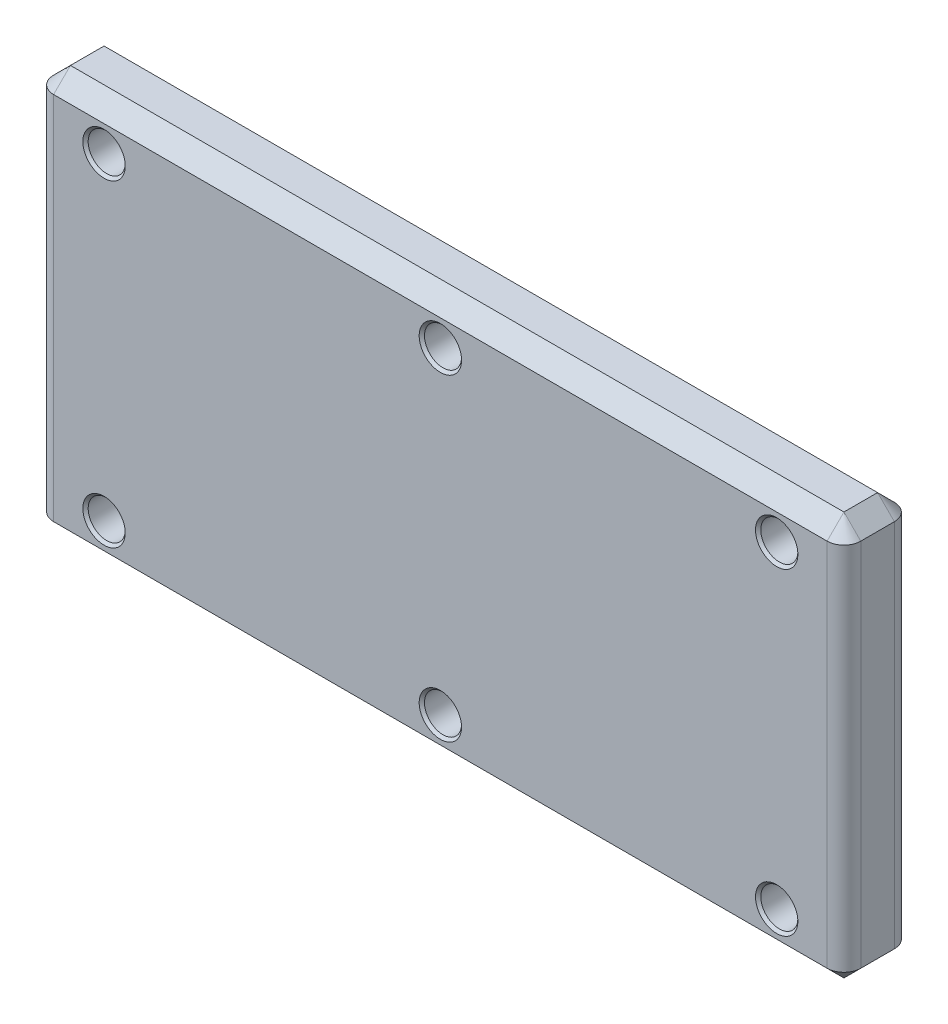
SolidWorks part; units mm, degrees
material "ABS"
ref_plane "Front Plane" through (0, 0, 0) normal (0, 0, 1) x (1, 0, 0)
ref_plane "Top Plane" through (0, 0, 0) normal (0, 1, 0) x (1, 0, 0)
ref_plane "Right Plane" through (0, 0, 0) normal (1, 0, 0) x (0, 0, -1)
ref_axis "X Axis" through (88.99, 0, 0) along (-1, 0, 0)
ref_axis "Y Axis" through (0, 55, 0) along (0, -1, 0)
ref_axis "Z Axis" through (0, 0, -88.99) along (0, 0, 1)
sketch "Sketch1" plane through (0, 0, 0) normal (0, 0, 1) x (1, 0, 0)
  line L1 (38.1, -19.05) -> (-38.1, -19.05)
  line L2 (38.1, -19.05) -> (38.1, 19.05)
  line L3 (38.1, 19.05) -> (-38.1, 19.05)
  line L4 (-38.1, -19.05) -> (-38.1, 19.05)
  line L5 (0, 19.05) -> (0, -19.05) construction
  line L6 (38.1, 0) -> (-38.1, 0) construction
  point P0 (0, 0)
  dimension "D1" = 76.2
  dimension "D2" = 38.1
extrude "Boss-Extrude1" add sketch "Sketch1" along normal mid plane 6.35
extrude "Boss-Extrude2" add sketch "Sketch1<2>" along normal mid plane 6.35
sketch "Sketch1<2>" plane through (0, 0, 0) normal (0, 0, 1) x (1, 0, 0) same geometry as "Sketch1"
sketch "Sketch8" plane through (0, 0, 0) normal (0, 1, 0) x (1, 0, 0)
  line L0 (-36.8427, 2.921) -> (-36.2505, 1.651) construction
  line L1 (-38.1, 3.175) -> (-33.02, 3.175)
  line L2 (-38.1, 3.175) -> (-38.1, 2.921)
  line L3 (-38.1, 2.921) -> (-33.02, 2.921) construction
  line L4 (-33.02, 3.175) -> (-33.02, 2.921)
  line L5 (-35.56, 2.921) -> (-35.56, 3.175) construction
  line L6 (-38.1, 3.048) -> (-33.02, 3.048) construction
  line L7 (-36.2505, 1.651) -> (-34.8695, 1.651) construction
  line L8 (-34.8695, 1.651) -> (-34.2773, 2.921) construction
  line L9 (-34.2773, 2.921) -> (-36.8427, 2.921) construction
  line L12 (-36.8507, 2.7016) -> (-36.4165, 1.7704)
  line L13 (-36.0721, 1.551) -> (-35.0479, 1.551)
  line L14 (-34.7035, 1.7704) -> (-34.2693, 2.7016)
  line L15 (-36.9333, 2.8787) -> (-36.3142, 1.551) construction
  line L16 (-34.8058, 1.551) -> (-34.1867, 2.8787) construction
  line L17 (-38.1, 2.921) -> (-37.1951, 2.921)
  line L18 (-33.9249, 2.921) -> (-33.02, 2.921)
  line L19 (-36.3142, 1.551) -> (-34.8058, 1.551) construction
  arc A0 (-34.2693, 2.7016) -> (-33.9249, 2.921) centre (-33.9249, 2.541) cw
  arc A1 (-35.0479, 1.551) -> (-34.7035, 1.7704) centre (-35.0479, 1.931) ccw
  arc A2 (-36.4165, 1.7704) -> (-36.0721, 1.551) centre (-36.0721, 1.931) ccw
  arc A3 (-36.8507, 2.7016) -> (-37.1951, 2.921) centre (-37.1951, 2.541) ccw
  point P6 (-35.56, 2.921)
  point P11 (-35.56, 1.651)
  point P20 (-34.167, 2.921)
  point P29 (-36.953, 2.921)
  point P48 (-35.56, 3.048)
  dimension "D6" = 0.1
  dimension "D7" = 0.38
  dimension "D1" = 50
  dimension "D2" = 1.27
  dimension "D3" = 2.5654
  dimension "D4" = 0.254
  dimension "D5" = 5.08
extrude "Cut-Extrude1" cut sketch "Sketch8" against normal mid plane 6.858 from offset 6.35 offset against normal yes
pattern_linear "LPattern1" count 15 spacing 5.08 along (1, 0, 0) count 2 spacing 12.7 along (0, 1, 0) of "Cut-Extrude1"
sketch "Sketch10" [suppressed] plane through (0, 0, -3.175) normal (0, 0, -1) x (-1, 0, 0)
  line L0 (-38.1, -19.05) -> (-38.1, 19.05) construction
  line L1 (-38.1, 9.779) -> (38.1, 9.779)
  line L2 (-38.1, 9.779) -> (-38.1, 2.921)
  line L3 (-38.1, 2.921) -> (38.1, 2.921)
  line L4 (38.1, 9.779) -> (38.1, 2.921)
  line L5 (0, 2.921) -> (0, 9.779) construction
  line L6 (-38.1, 6.35) -> (38.1, 6.35) construction
  line L7 (38.1, 19.05) -> (38.1, -19.05) construction
  line L8 (0, 2.921) -> (0, -2.921) construction
  line L9 (-38.1, -2.921) -> (38.1, -2.921)
  line L10 (-38.1, -2.921) -> (-38.1, -9.779)
  line L11 (-38.1, -9.779) -> (38.1, -9.779)
  line L12 (38.1, -2.921) -> (38.1, -9.779)
  line L13 (0, -9.779) -> (0, -2.921) construction
  line L14 (-38.1, -6.35) -> (38.1, -6.35) construction
  point P14 (0, 0)
  point P76 (0, 6.35)
  point P81 (0, -6.35)
  dimension "D1" = 6.858
  dimension "D2" = 12.7
extrude "Cut-Extrude2" [suppressed] cut sketch "Sketch10" against normal blind 0.254
sketch "Sketch2" plane through (0, 0, 0) normal (0, 0, 1) x (1, 0, 0)
  line L1 (31.75, -15) -> (-31.75, -15) construction
  line L2 (31.75, -15) -> (31.75, 15) construction
  line L3 (31.75, 15) -> (-31.75, 15) construction
  line L4 (-31.75, -15) -> (-31.75, 15) construction
  line L5 (0, 15) -> (0, -15) construction
  line L6 (31.75, 0) -> (-31.75, 0) construction
  point P0 (0, 0)
  dimension "D1" = 63.5
  dimension "D2" = 30
sketch "Sketch5" plane through (0, 0, 3.175) normal (0, 0, 1) x (1, 0, 0)
  point P0 (-31.75, 15)
  point P3 (-31.75, -15)
  point P6 (0, 15)
  point P9 (0, -15)
  point P12 (31.75, 15)
  point P15 (31.75, -15)
hole_wizard "M3 Clearance Hole1" positions "Sketch5" profile "Sketch4" hole size "M3" standard "ANSI Metric" end condition up to next
sketch "Sketch4" plane through (-31.75, 15, 3.175) normal (1, 0, 0) x (0, -1, 0)
  line L0 (0, 0) -> (0, 6.35)
  line L1 (0, 6.35) -> (2, 6.35)
  line L2 (1.75, 6.1) -> (1.75, 0.25)
  line L3 (1.75, 0.25) -> (2, 0)
  line L5 (2, 0) -> (0, 0)
  line L6 (-1.75, 0.25) -> (-2, 0) construction
  line L7 (2, 6.35) -> (1.75, 6.1)
  line L8 (-2, 6.35) -> (-1.75, 6.1) construction
  line L11 (0, -6.35) -> (0, 107.95) construction
  dimension "Thru Hole Dia." = 3.5
  dimension "Thru Hole Depth" = 6.35
  dimension "Near C'Sink Dia." = 4
  dimension "Near C'Sink Angle" = 90
  dimension "Far C'Sink Dia." = 4
  dimension "Far C'Sink Angle" = 90
fillet "Fillet1" radius 1.5875 4 edges at (-38.1, -14.4145, -3.175) (-38.1, 0, 3.175) (38.1, 0, 3.175) (38.1, -14.4145, -3.175)
chamfer "Chamfer1" distance 1.5875 angle 45 16 edges at (-38.1, 19.05, 0) (-37.635, 19.05, 2.71) (-37.635, 19.05, -2.71) (0, 19.05, 3.175) (0, 19.05, -3.175) (37.635, 19.05, 2.71) (37.635, 19.05, -2.71) (38.1, 19.05, 0) (-38.1, -19.05, 0) (-37.635, -19.05, 2.71) (-37.635, -19.05, -2.71) (0, -19.05, 3.175) (0, -19.05, -3.175) (37.635, -19.05, 2.71) (37.635, -19.05, -2.71) (38.1, -19.05, 0)
chamfer "Chamfer2" distance 0.254 angle 45 12 edges at (36.9615, -9.779, -3.1102) (-36.9615, -9.779, -3.1102) (0, -9.779, -3.175) (36.9615, -2.921, -3.1102) (-36.9615, -2.921, -3.1102) (0, -2.921, -3.175) (36.9615, 2.921, -3.1102) (-36.9615, 2.921, -3.1102) (0, 2.921, -3.175) (36.9615, 9.779, -3.1102) (-36.9615, 9.779, -3.1102) (0, 9.779, -3.175)
chamfer "Chamfer3" [suppressed] distance 0.254 angle 45
